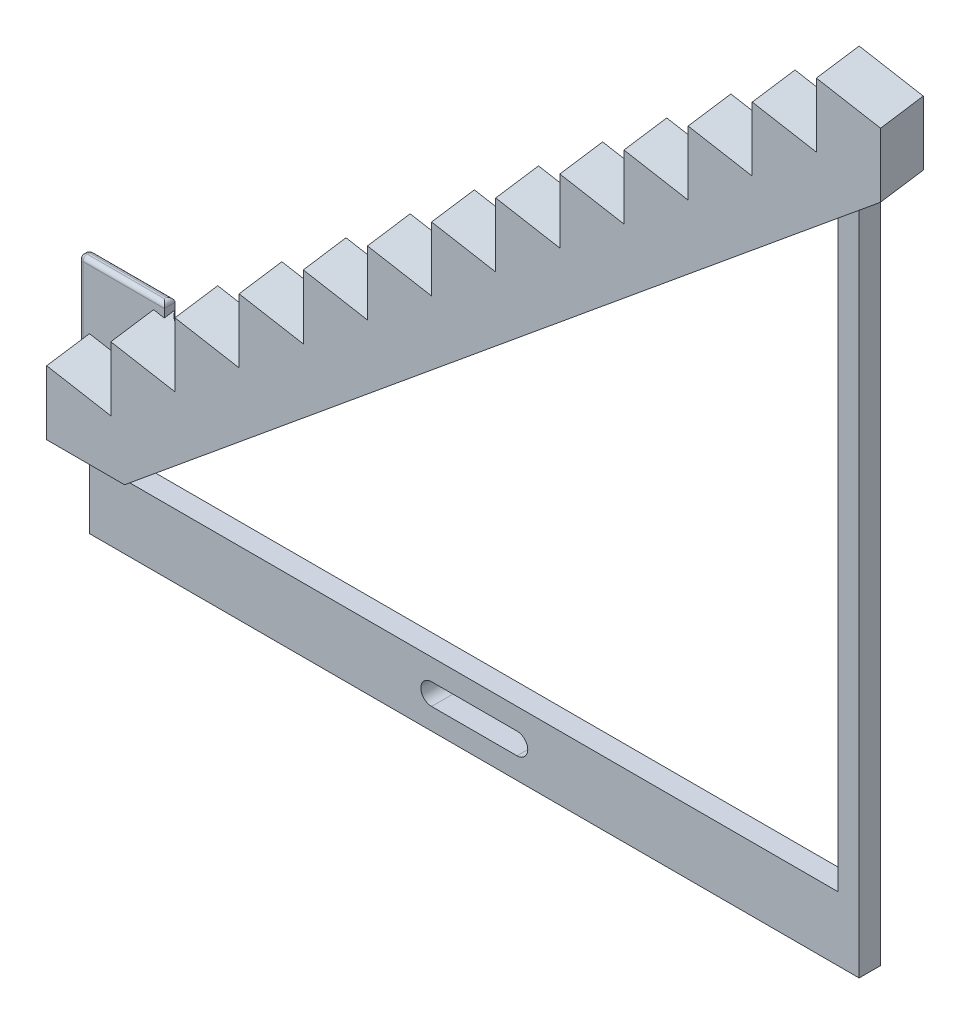
SolidWorks part; units mm, degrees
ref_plane "Front Plane" through (0, 0, 0) normal (0, 0, 1) x (1, 0, 0)
ref_plane "Top Plane" through (0, 0, 0) normal (0, 1, 0) x (1, 0, 0)
ref_plane "Right Plane" through (0, 0, 0) normal (1, 0, 0) x (0, 0, -1)
sketch "Sketch1" plane through (0, 0, 0) normal (0, 0, 1) x (1, 0, 0)
  line L0 (0, 0) -> (-30, 5.2898)
  line L1 (-30, 5.2898) -> (-30, -24.7102)
  line L2 (-30, -24.7102) -> (-60, -19.4204)
  line L3 (-60, -19.4204) -> (-60, -49.4204)
  line L4 (-60, -49.4204) -> (-90, -44.1306)
  line L5 (-90, -44.1306) -> (-90, -74.1306)
  line L6 (-90, -74.1306) -> (-120, -68.8408)
  line L7 (-120, -68.8408) -> (-120, -98.8408)
  line L8 (-120, -98.8408) -> (-150, -93.551)
  line L9 (-150, -93.551) -> (-150, -123.551)
  line L10 (-150, -123.551) -> (-180, -118.2611)
  line L11 (-180, -118.2611) -> (-180, -148.2611)
  line L12 (-180, -148.2611) -> (-210, -142.9713)
  line L13 (-210, -142.9713) -> (-210, -172.9713)
  line L14 (-210, -172.9713) -> (-240, -167.6815)
  line L15 (-240, -167.6815) -> (-240, -197.6815)
  line L16 (-240, -197.6815) -> (-270, -192.3917)
  line L17 (-270, -192.3917) -> (-270, -222.3917)
  line L18 (-270, -222.3917) -> (-300, -217.1019)
  line L19 (-300, -217.1019) -> (-300, -247.1019)
  line L20 (-300, -247.1019) -> (-330, -241.8121)
  line L21 (-330, -241.8121) -> (-330, -271.8121)
  line L22 (-330, -271.8121) -> (-360, -266.5223)
  line L23 (-360, -266.5223) -> (-360, -296.5223)
  line L24 (-360, -296.5223) -> (-390, -291.2325)
  line L25 (-390, -291.2325) -> (-390, -321.2325)
  line L26 (0, 0) -> (-390, -321.2325) construction
  line L27 (0, -30) -> (-353.5778, -321.2325)
  line L28 (0, -30) -> (0, 0)
  line L29 (-353.5778, -321.2325) -> (-390, -321.2325)
  dimension "D1" = 30
  dimension "D2" = 30
  dimension "D3" = 100
  dimension "D4" = 30
ref_plane "Plane1" through (0, 0, 20) normal (0, 0, 1) x (1, 0, 0)
sketch "Sketch2" plane through (0, 0, 20) normal (0, 0, 1) x (1, 0, 0)
  line L0 (0, 0) -> (-390, -321.2325) construction
  line L29 (-353.5778, -324.2325) -> (-390, -324.2325)
  line L30 (-390, -294.2325) -> (-390, -324.2325)
  line L31 (-360, -299.5223) -> (-390, -294.2325)
  line L32 (-360, -269.5223) -> (-360, -299.5223)
  line L33 (-330, -274.8121) -> (-360, -269.5223)
  line L34 (-330, -244.8121) -> (-330, -274.8121)
  line L35 (-300, -250.1019) -> (-330, -244.8121)
  line L36 (-300, -220.1019) -> (-300, -250.1019)
  line L37 (-270, -225.3917) -> (-300, -220.1019)
  line L38 (-270, -195.3917) -> (-270, -225.3917)
  line L39 (-240, -200.6815) -> (-270, -195.3917)
  line L40 (-240, -170.6815) -> (-240, -200.6815)
  line L41 (-210, -175.9713) -> (-240, -170.6815)
  line L42 (-210, -145.9713) -> (-210, -175.9713)
  line L43 (-180, -151.2611) -> (-210, -145.9713)
  line L44 (-180, -121.2611) -> (-180, -151.2611)
  line L45 (-150, -126.551) -> (-180, -121.2611)
  line L46 (-150, -96.551) -> (-150, -126.551)
  line L47 (-120, -101.8408) -> (-150, -96.551)
  line L48 (-120, -71.8408) -> (-120, -101.8408)
  line L49 (-90, -77.1306) -> (-120, -71.8408)
  line L50 (-90, -47.1306) -> (-90, -77.1306)
  line L51 (-60, -52.4204) -> (-90, -47.1306)
  line L52 (-60, -22.4204) -> (-60, -52.4204)
  line L53 (-30, -27.7102) -> (-60, -22.4204)
  line L54 (-30, 2.2898) -> (-30, -27.7102)
  line L55 (0, -3) -> (-30, 2.2898)
  line L56 (0, -33) -> (-353.5778, -324.2325)
  line L57 (0, -33) -> (0, -3)
  dimension "D1" = 30
  dimension "D2" = 30
  dimension "D3" = 100
  dimension "D4" = 30
  dimension "D5" = 3
loft "Loft1" add profiles "Sketch1", "Sketch2" connector at (-270, -192.3917, 0) connector at (-270, -195.3917, 20)
ref_plane "Plane2" through (0, -324.2325, 0) normal (0, 1, 0) x (1, 0, 0)
sketch "Sketch3" plane through (0, -324.2325, 0) normal (0, 1, 0) x (1, 0, 0)
  line L0 (-390, -20) -> (-353.5778, -20) construction
  line L1 (-375, -15) -> (-365, -15)
  line L2 (-375, -15) -> (-375, -5)
  line L3 (-375, -5) -> (-365, -5)
  line L4 (-365, -15) -> (-365, -5)
  line L5 (-390, 0) -> (-390, -20) construction
  dimension "D1" = 10
  dimension "D2" = 10
  dimension "D3" = 5
  dimension "D4" = 15
extrude "Boss-Extrude1" add sketch "Sketch3" along normal blind 10 and the other way blind 33
sketch "Sketch4" plane through (0, -324.2325, 0) normal (0, 1, 0) x (1, 0, 0)
  line L0 (0, 0) -> (0, -20) construction
  line L1 (-25, -15) -> (-15, -15)
  line L2 (-25, -15) -> (-25, -5)
  line L3 (-25, -5) -> (-15, -5)
  line L4 (-15, -15) -> (-15, -5)
  line L5 (-55, -20) -> (55, -20) construction
  dimension "D1" = 15
  dimension "D2" = 10
  dimension "D3" = 10
  dimension "D4" = 5
extrude "Boss-Extrude2" add sketch "Sketch4" along normal blind 300 and the other way blind 33
sketch "Sketch5" plane through (0, 0, 5) normal (0, 0, -1) x (-1, 0, 0)
  line L1 (15, -357.2325) -> (375, -357.2325)
  line L2 (15, -357.2325) -> (15, -327.2325)
  line L3 (15, -327.2325) -> (375, -327.2325)
  line L4 (375, -357.2325) -> (375, -327.2325)
  line L5 (195, -327.2325) -> (195, -357.2325) construction
  line L6 (15, -342.2325) -> (375, -342.2325) construction
  line L7 (175, -342.2325) -> (215, -342.2325) construction
  line L8 (175, -337.2325) -> (215, -337.2325)
  line L9 (175, -347.2325) -> (215, -347.2325)
  arc A0 (175, -337.2325) -> (175, -347.2325) centre (175, -342.2325) ccw
  arc A1 (215, -347.2325) -> (215, -337.2325) centre (215, -342.2325) ccw
  point P11 (195, -342.2325)
  dimension "D1" = 30
  dimension "D2" = 360
  dimension "D3" = 10
  dimension "D4" = 40
extrude "Boss-Extrude3" add sketch "Sketch5" against normal blind 10
sketch "Sketch6" plane through (0, 0, 0) normal (0, 0, -1) x (-1, 0, 0)
  line L0 (360, -296.5223) -> (360, -266.5223) construction
  line L1 (360, -266.5223) -> (360, -296.5223) construction
  line L2 (360, -266.5223) -> (390, -266.5223) construction
  line L3 (390, -266.5223) -> (390, -291.2325) construction
  line L4 (390, -291.2325) -> (360, -296.5223) construction
  line L5 (355, -302.4811) -> (355, -261.5223)
  line L6 (355, -261.5223) -> (395, -261.5223)
  line L7 (395, -261.5223) -> (395, -295.428)
  line L8 (395, -295.428) -> (355, -302.4811)
  point P12 (0, 0)
  dimension "D1" = 5
extrude "Boss-Extrude4" add sketch "Sketch6" along normal blind 5
fillet "Fillet1" radius 10 2 edges
fillet "Fillet2" radius 2 7 edges at (-395, -295.428, -2.5) (-395, -278.4751, -5) (-395, -261.5223, -2.5) (-395, -278.4751, 0) (-375, -261.5223, 0) (-355, -261.5223, -2.5) (-375, -261.5223, -5)
